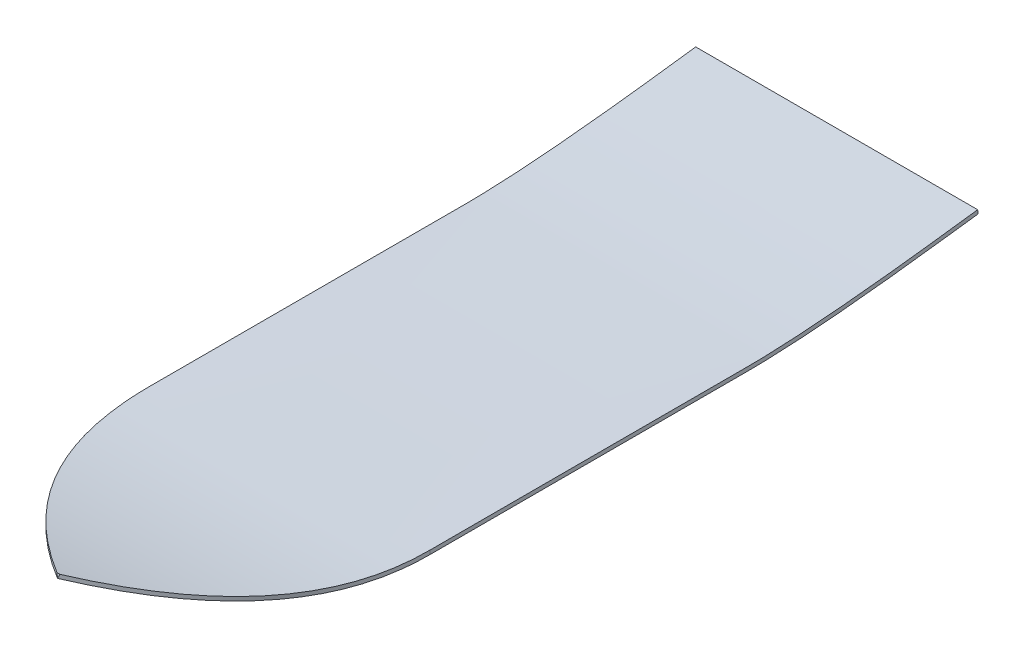
SolidWorks part; units mm, degrees
ref_plane "Front Plane" through (0, 0, 0) normal (0, 0, 1) x (1, 0, 0)
ref_plane "Top Plane" through (0, 0, 0) normal (0, 1, 0) x (1, 0, 0)
ref_plane "Right Plane" through (0, 0, 0) normal (1, 0, 0) x (0, 0, -1)
sketch "Sketch1" plane through (0, 0, 0) normal (1, 0, 0) x (0, 0, -1)
  line L16 (-2503.2333, 184.2816) -> (-2509.3541, 160.0424)
  line L17 (2465.1921, 161.4304) -> (2467.2931, 136.5188)
  spline S0 degree 3 poles (-2503.2333, 184.2816) (-2291.5036, 130.8164) (-1972.7147, 74.8823) (-1498.5338, 35.6026) (-1252.9374, 28.0828) (-1102.4537, 27.6877) (-1068.1473, 27.6945) (-965.237, 27.7068) (-786.8559, 27.731) (-409.5114, 27.7822) (2.1371, 27.8381) (468.6721, 27.9014) (748.25, 27.9408) (921.4857, 27.9596) (959.2198, 27.9707) (966.0793, 27.9855) (971.2315, 27.9281) (981.5821, 27.8587) (1053.0395, 27.6572) (1188.2679, 31.1867) (1808.7552, 68.0386) (2414.5395, 157.1584) (2465.1921, 161.4304) knots 0.002418 0.002418 0.002418 0.002418 0.15625 0.21875 0.296875 0.300781 0.304688 0.316406 0.359375 0.40625 0.53125 0.59375 0.671875 0.69043 0.692383 0.693359 0.694336 0.695312 0.699219 0.734375 0.765625 1 1 1 1
  spline S1 degree 1 poles (-2509.3541, 160.0424) (2467.2931, 136.5188) knots 0 0 1 1 construction
  spline S2 degree 3 poles (-2509.3541, 160.0424) (-2503.952, 158.6783) (-2493.1525, 155.9738) (-2471.4524, 150.6295) (-2444.1929, 144.0842) (-2411.249, 136.4418) (-2367.0202, 126.5357) (-2311.1618, 114.6847) (-2243.2172, 101.3139) (-2174.3577, 88.793) (-2081.3255, 73.2313) (-1962.7483, 55.9025) (-1816.7966, 38.5028) (-1667.1854, 24.4954) (-1513.9137, 13.8787) (-1383.1371, 7.8553) (-1276.6842, 4.73) (-1209.3914, 3.4809) (-1155.093, 2.9066) (-1120.981, 2.7194) (-1093.5403, 2.6856) (-1066.1601, 2.6968) (-1031.9417, 2.6981) (-990.8762, 2.7041) (-936.123, 2.7108) (-840.3039, 2.7238) (-703.4196, 2.7424) (-539.1584, 2.7646) (-374.8971, 2.7869) (-210.6359, 2.8092) (-46.3747, 2.8315) (117.8865, 2.8538) (282.1477, 2.8761) (419.0321, 2.8948) (528.5395, 2.91) (610.6701, 2.9213) (692.8005, 2.9323) (774.9311, 2.9428) (843.3728, 2.9509) (891.283, 2.9563) (918.6612, 2.9608) (934.0614, 2.964) (944.3288, 2.9665) (949.4616, 2.9679) (954.598, 2.9693) (958.8897, 2.972) (962.3378, 2.978) (964.8277, 2.9801) (967.2164, 2.9689) (969.7363, 2.9445) (972.3765, 2.9205) (975.8639, 2.8966) (980.2056, 2.8729) (985.4463, 2.852) (992.4579, 2.835) (1004.8013, 2.8336) (1022.6288, 2.9124) (1044.3203, 3.1325) (1073.6208, 3.5892) (1110.9215, 4.4572) (1156.6494, 5.9476) (1218.7579, 8.4976) (1298.2421, 12.6735) (1395.6631, 19.0557) (1494.2017, 26.5992) (1592.9326, 35.0943) (1723.5938, 47.4109) (1850.9279, 60.794) (1971.213, 74.4073) (2056.9704, 84.5234) (2137.339, 94.3364) (2211.3853, 103.6372) (2278.1744, 112.2165) (2327.0034, 118.59) (2361.4982, 123.1181) (2384.9659, 126.2024) (2405.9102, 128.9483) (2424.2081, 131.3289) (2437.1445, 132.9854) (2446.0358, 134.0998) (2451.9547, 134.8263) (2457.0999, 135.4392) (2460.7175, 135.8513) (2463.1847, 136.1189) (2464.8141, 136.2878) (2465.9703, 136.4005) (2466.7788, 136.4745) (2467.1161, 136.5039) (2467.2931, 136.5188) knots 0.002418 0.002418 0.002418 0.002418 0.006315 0.010212 0.018006 0.025799 0.033593 0.04918 0.064767 0.080354 0.095942 0.127116 0.15829 0.189465 0.220639 0.251814 0.267401 0.282988 0.290782 0.298575 0.302472 0.306369 0.314163 0.321956 0.32975 0.345337 0.376511 0.407686 0.43886 0.470035 0.501209 0.532384 0.563558 0.594732 0.61032 0.625907 0.641494 0.657081 0.672669 0.680462 0.684359 0.688256 0.68923 0.690204 0.691178 0.692153 0.69264 0.693127 0.693614 0.694101 0.694588 0.695075 0.696049 0.697024 0.697998 0.699946 0.703843 0.70774 0.711637 0.71943 0.727224 0.735017 0.750605 0.766192 0.781779 0.797366 0.812953 0.844128 0.859715 0.875302 0.89089 0.906477 0.922064 0.937651 0.945445 0.953238 0.961032 0.968826 0.976619 0.980516 0.984413 0.98831 0.992206 0.994155 0.996103 0.998052 0.999026 1 1 1 1
  dimension "D1" = 25
extrude "Boss-Extrude1" add sketch "Sketch1" along normal blind 1524 and the other way blind 1524
sketch "Sketch3" plane through (0, 0, 0) normal (0, 1, 0) x (1, 0, 0)
  line L0 (-900, 2487.8819) -> (900, 2487.8819)
  line L1 (-900, 2487.8819) -> (-900, -1029.6517)
  line L2 (900, 2487.8819) -> (900, -1029.6517)
  line L3 (0, 2955.5244) -> (0, -2061.9995) construction
  line L4 (-2934.2017, 4085.2419) -> (2797.2556, 4085.2419)
  line L5 (-2934.2017, 4085.2419) -> (-2934.2017, -3918.064)
  line L6 (-2934.2017, -3918.064) -> (2797.2556, -3918.064)
  line L7 (2797.2556, 4085.2419) -> (2797.2556, -3918.064)
  line L8 (-94.9374, 0) -> (0, 0) construction
  line L11 (-1524, 1954.9582) -> (1524, 1954.9582) construction
  spline S0 degree 2 poles (-900, -1029.6517) (-900, -1904.2903) (0, -2509.3541) knots 0 0 0 1 1 1
  spline S1 degree 2 poles (900, -1029.6517) (900, -1904.2903) (0, -2509.3541) knots 0 0 0 1 1 1
  dimension "D1" = 1800
extrude "Cut-Extrude1" cut sketch "Sketch3" against normal through all both and the other way through all
